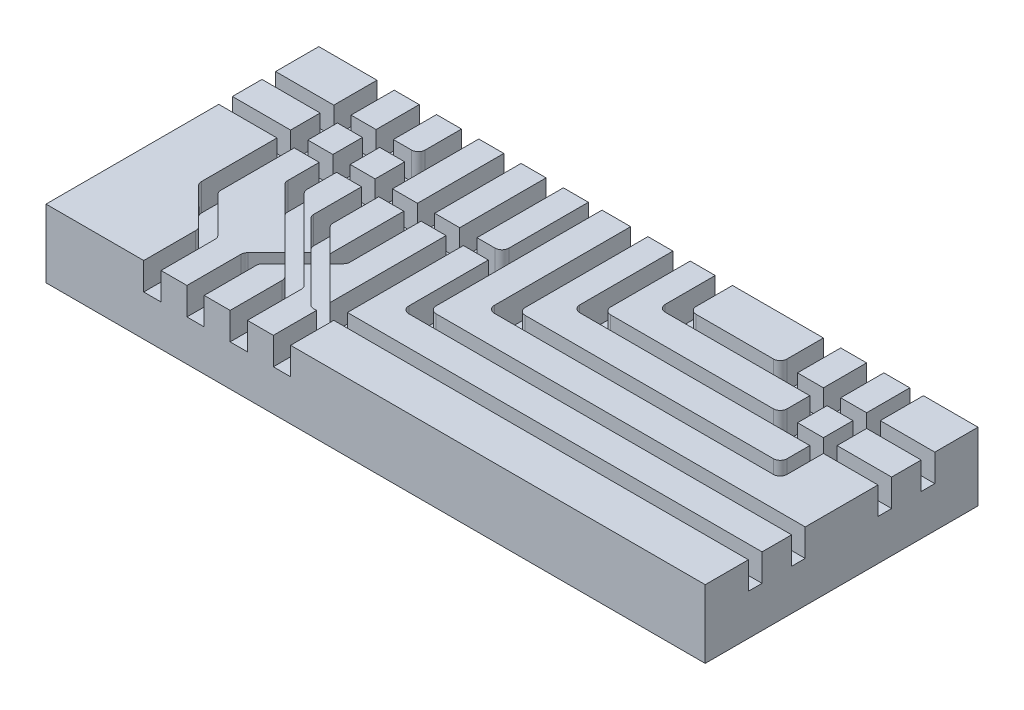
SolidWorks part; units mm, degrees
ref_plane "Front Plane" through (0, 0, 0) normal (0, 0, 1) x (1, 0, 0)
ref_plane "Top Plane" through (0, 0, 0) normal (0, 1, 0) x (1, 0, 0)
ref_plane "Right Plane" through (0, 0, 0) normal (1, 0, 0) x (0, 0, -1)
sketch "Sketch1" plane through (0, 0, 0) normal (0, 1, 0) x (1, 0, 0)
  line L1 (0, 0) -> (145, 0)
  line L2 (0, 0) -> (0, 60)
  line L3 (0, 60) -> (145, 60)
  line L4 (145, 0) -> (145, 60)
  dimension "D1" = 60
  dimension "D2" = 145
extrude "ProfileBoss-Extrude1" add sketch "Sketch1" along normal blind 15
sketch "Sketch2" plane through (0, 15, 0) normal (0, 1, 0) x (1, 0, 0)
  line L0 (25.9, 60) -> (22.1, 60)
  line L1 (53.8, 60) -> (53.8, 41)
  line L7 (53.8, 0) -> (50, 0)
  line L9 (16.6, 60) -> (12.8, 60)
  line L14 (72.4, 60) -> (72.4, 31.5)
  line L15 (72.4, 31.5) -> (130, 31.5)
  line L16 (130, 31.5) -> (130, 38)
  line L17 (130, 60) -> (133, 60)
  line L18 (133, 60) -> (133, 50.5)
  line L19 (133, 28.5) -> (68.6, 28.5)
  line L20 (68.6, 28.5) -> (68.6, 60)
  line L21 (68.6, 60) -> (72.4, 60)
  line L22 (77.9, 60) -> (77.9, 38)
  line L24 (124.3, 41) -> (124.3, 47.5)
  line L25 (124.3, 60) -> (120.5, 60)
  line L26 (120.5, 60) -> (120.5, 50.5)
  line L28 (81.7, 41) -> (81.7, 60)
  line L29 (81.7, 60) -> (77.9, 60)
  line L30 (87.2, 60) -> (87.2, 47.5)
  line L32 (114.8, 50.5) -> (114.8, 60)
  line L33 (114.8, 60) -> (111, 60)
  line L34 (111, 60) -> (111, 50.5)
  line L36 (91, 50.5) -> (91, 60)
  line L37 (91, 60) -> (87.2, 60)
  line L39 (50, 60) -> (53.8, 60)
  line L41 (21.5, 0) -> (25.3, 0)
  line L46 (145, 0) -> (145, 60) construction
  line L51 (44.5, 60) -> (40.7, 60)
  line L52 (145, 60) -> (0, 60) construction
  line L53 (34.8, 0) -> (31, 0)
  line L54 (40.5, 0) -> (44.3, 0)
  line L58 (50, 0) -> (50, 9.5)
  line L63 (0, 0) -> (145, 0) construction
  line L66 (91, 50.5) -> (111, 50.5)
  line L67 (87.2, 47.5) -> (120.5, 47.5)
  line L68 (145, 50.5) -> (145, 47.5)
  line L69 (114.8, 50.5) -> (120.5, 50.5)
  line L70 (120.5, 47.5) -> (120.5, 41)
  line L71 (124.3, 50.5) -> (124.3, 60)
  line L72 (124.3, 47.5) -> (130, 47.5)
  line L73 (124.3, 50.5) -> (130, 50.5)
  line L74 (133, 50.5) -> (145, 50.5)
  line L75 (130, 50.5) -> (130, 60)
  line L76 (133, 47.5) -> (145, 47.5)
  line L77 (133, 47.5) -> (133, 41)
  line L78 (81.7, 41) -> (120.5, 41)
  line L79 (145, 41) -> (145, 38)
  line L80 (145, 38) -> (133, 38)
  line L81 (124.3, 41) -> (130, 41)
  line L82 (130, 41) -> (130, 47.5)
  line L83 (133, 41) -> (145, 41)
  line L84 (130, 38) -> (77.9, 38)
  line L85 (133, 38) -> (133, 28.5)
  line L86 (59.3, 60) -> (62.3, 60)
  line L87 (62.3, 60) -> (62.3, 22)
  line L88 (62.3, 22) -> (145, 22)
  line L89 (145, 22) -> (145, 19)
  line L90 (145, 19) -> (59.3, 19)
  line L91 (59.3, 19) -> (59.3, 38)
  line L93 (145, 12.5) -> (145, 9.5)
  line L94 (145, 9.5) -> (53.8, 9.5)
  line L95 (16.6, 60) -> (16.6, 50.5)
  line L97 (25.3, 12.5) -> (25.3, 0)
  line L98 (21.5, 0) -> (21.5, 12.0574)
  line L100 (12.8, 20.7574) -> (12.8, 38)
  line L101 (22.1, 60) -> (22.1, 50.5)
  line L104 (25.9, 60) -> (25.9, 50.5)
  line L109 (40.7, 60) -> (40.7, 41)
  line L110 (44.5, 60) -> (44.5, 41)
  line L113 (40.5, 12.0574) -> (40.5, 0)
  line L117 (50, 12.5) -> (50, 38)
  line L118 (53.8, 12.5) -> (145, 12.5)
  line L120 (53.8, 9.5) -> (53.8, 0)
  line L121 (31.4, 26.8574) -> (31.4, 38)
  line L122 (31.4, 60) -> (35.2, 60)
  line L123 (35.2, 60) -> (35.2, 41)
  line L134 (50, 12.5) -> (42.6213, 19.8787)
  line L135 (44.3, 12.5) -> (39.7713, 17.0287)
  line L140 (22.1, 30.4574) -> (35.5287, 17.0287)
  line L141 (50, 9.5) -> (48.7574, 9.5)
  line L143 (31.4, 26.8574) -> (38.3787, 19.8787)
  line L144 (31, 0) -> (31, 12.5)
  line L145 (34.8, 0) -> (34.8, 12.0574)
  line L146 (44.3, 0) -> (44.3, 12.5)
  line L147 (31, 12.5) -> (35.5287, 17.0287)
  line L148 (44.5, 21.7574) -> (42.6213, 19.8787)
  line L149 (25.3, 12.5) -> (16.6, 21.2)
  line L150 (21.5, 12.0574) -> (12.8, 20.7574)
  line L151 (37.65, 19.15) -> (38.3787, 19.8787)
  line L152 (37.65, 14.9074) -> (40.5, 12.0574)
  line L153 (37.65, 19.15) -> (25.9, 30.9)
  line L154 (40.7, 21.8) -> (35.2, 27.3)
  line L155 (40.5, 17.7574) -> (39.7713, 17.0287)
  line L156 (40.5, 17.7574) -> (48.7574, 9.5)
  line L157 (37.65, 14.9074) -> (34.8, 12.0574)
  line L158 (31.4, 50.5) -> (25.9, 50.5)
  line L159 (0, 60) -> (0, 0) construction
  line L160 (0, 50.5) -> (0, 47.5)
  line L161 (0, 47.5) -> (12.8, 47.5)
  line L162 (59.3, 41) -> (53.8, 41)
  line L163 (0, 41) -> (0, 38)
  line L164 (0, 38) -> (12.8, 38)
  line L165 (12.8, 50.5) -> (12.8, 60)
  line L166 (16.6, 47.5) -> (22.1, 47.5)
  line L167 (16.6, 47.5) -> (16.6, 41)
  line L168 (12.8, 50.5) -> (0, 50.5)
  line L169 (22.1, 50.5) -> (16.6, 50.5)
  line L170 (25.9, 47.5) -> (31.4, 47.5)
  line L171 (22.1, 47.5) -> (22.1, 41)
  line L172 (25.9, 47.5) -> (25.9, 41)
  line L173 (31.4, 50.5) -> (31.4, 60)
  line L174 (12.8, 41) -> (0, 41)
  line L175 (16.6, 38) -> (22.1, 38)
  line L176 (12.8, 41) -> (12.8, 47.5)
  line L177 (16.6, 38) -> (16.6, 21.2)
  line L178 (22.1, 38) -> (22.1, 30.4574)
  line L179 (25.9, 38) -> (25.9, 30.9)
  line L180 (22.1, 41) -> (16.6, 41)
  line L181 (25.9, 38) -> (31.4, 38)
  line L182 (31.4, 41) -> (31.4, 47.5)
  line L183 (31.4, 41) -> (25.9, 41)
  line L184 (35.2, 38) -> (35.2, 27.3)
  line L185 (35.2, 38) -> (40.7, 38)
  line L186 (40.7, 38) -> (40.7, 21.8)
  line L187 (44.5, 38) -> (44.5, 21.7574)
  line L188 (40.7, 41) -> (35.2, 41)
  line L189 (44.5, 38) -> (50, 38)
  line L190 (53.8, 38) -> (59.3, 38)
  line L191 (50, 41) -> (50, 60)
  line L192 (53.8, 38) -> (53.8, 12.5)
  line L193 (59.3, 41) -> (59.3, 60)
  line L194 (50, 41) -> (44.5, 41)
  point P104 (-44.2777, 79.5421)
  dimension "D2" = 9.3
  dimension "D4" = 9.5
  dimension "D5" = 9.3
  dimension "D3" = 9.5
  dimension "D1" = 3
  dimension "D9" = 12
  dimension "D10" = 20
  dimension "D8" = 9.3
  dimension "D13" = 3
  dimension "D19" = 12.8
  dimension "D14" = 9.5
  dimension "D15" = 9.5
  dimension "D16" = 9.5
  dimension "D18" = 9.5
  dimension "D7" = 9.3
  dimension "D12" = 9.3
  dimension "D21" = 3
  dimension "D22" = 9.5
  dimension "D17" = 9.3
  dimension "D20" = 3
  dimension "D23" = 135
  dimension "D24" = 3
  dimension "D25" = 135
  dimension "D26" = 3
  dimension "D27" = 9.5
  dimension "D28" = 9.5
  dimension "D29" = 9.5
  dimension "D30" = 95
  dimension "D31" = 9.5
  dimension "D11" = 9.3
  dimension "D32" = 9.3
extrude "LeedCut-Extrude1" cut sketch "Sketch2" against normal blind 6
sketch "MountHoleSketch3" plane through (0, 0, 0) normal (0, 1, 0) x (1, 0, 0)
  line L0 (0, 60) -> (0, 50.5) construction
  line L2 (12.8, 60) -> (0, 60) construction
  line L3 (145, 0) -> (145, 9.5) construction
  circle A0 centre (6, 30) radius 2.05
  circle A1 centre (139, 30) radius 2.05
  dimension "D4" = 4.1
  dimension "D3" = 30
  dimension "D2" = 133
  dimension "D5" = 6
fillet "Fillet1" radius 1.5 8 edges at (87.2, 12, -47.5) (59.3, 12, -19) (68.6, 12, -28.5) (77.9, 12, -38) (62.3, 12, -22) (72.4, 12, -31.5) (81.7, 12, -41) (91, 12, -50.5)
fillet "Fillet2" radius 1.5 6 edges at (130, 12, -31.5) (120.5, 12, -41) (111, 12, -50.5) (133, 12, -28.5) (59.3, 12, -41) (31.4, 12, -50.5)
fillet "Fillet3" radius 1.5 14 edges at (25.3, 12, -12.5) (34.8, 12, -12.0574) (31.4, 12, -26.8574) (12.8, 12, -20.7574) (21.5, 12, -12.0574) (31, 12, -12.5) (44.3, 12, -12.5) (40.5, 12, -12.0574) (48.7574, 12, -9.5) (16.6, 12, -21.2) (35.2, 12, -27.3) (25.9, 12, -30.9) (22.1, 12, -30.4574) (44.5, 12, -21.7574)
extrude "MountHoleCut-Extrude2" cut sketch "MountHoleSketch3" against normal blind 0.1 and the other way blind 3.1
equation "\"D2@Sketch1\" = \"PowerCableGuideWidth\""
equation "\"PowerCableGuideWidth\"= IIF ( \"DistanceBetween24vPowerSupplyLeads\" * \"NumberOfPowerLeadSpaces\" + \"PowerCableDiameter\" * 2 + \"DistanceFromCaseToFirstPowerTerminal\" + \"PowerCableGuideMountSupportWidth\" * 2 , 145mm , 145mm )'Keep the width 145mm based on the original Distanceetween24vPowerSupplyLeads being 9.5mm"
equation "\"PowerCableGuideLength\"= 60mm"
equation "\"PowerCableDiameter\"= 3mm"
equation "\"NumberOfPowerLeadSpaces\"= 10"
equation "\"M3HeatInsertHoleDiameter\"= 4mm + .1mm'Add .1mm for printing"
equation "\"DistanceBetween24vPowerSupplyLeads\"= 9.3mm'Spec"
equation "\"PowerCableGuideDepth\"= 15mm"
equation "\"DistanceFromCaseToFirstPowerTerminal\"= 13mm + \"PowreCableGuideAdditionalPowerWidth\""
equation "\"PowerCableGuideMountSupportWidth\"= 12mm"
equation "\"D1@Sketch1\"=\"PowerCableGuideLength\""
equation "\"D1@ProfileBoss-Extrude1\" = \"PowerCableGuideDepth\""
equation "\"D1@LeedCut-Extrude1\" = \"PowerCableDiameter\" * 2"
equation "\"D2@Sketch2\"=\"DistanceBetween24vPowerSupplyLeads\""
equation "\"D4@Sketch2\"=\"DistanceBetweenOutgoingPowerSupplyLeeds\""
equation "\"D5@Sketch2\"=\"DistanceBetween24vPowerSupplyLeads\""
equation "\"D3@Sketch2\"=\"DistanceBetweenOutgoingPowerSupplyLeeds\""
equation "\"D1@Sketch2\"=\"PowerCableDiameter\""
equation "\"D8@Sketch2\"=\"DistanceBetween24vPowerSupplyLeads\""
equation "\"D9@Sketch2\"=\"PowerCableGuideMountSupportWidth\""
equation "\"D13@Sketch2\"=\"PowerCableDiameter\""
equation "\"D10@Sketch2\"=\"DistanceFromCaseToFirstPowerTerminal\""
equation "\"PowreCableGuideAdditionalPowerWidth\"= 7mm"
equation "\"D3@MountHoleSketch3\" = \"PowerCableGuideLength\" / 2"
equation "\"D4@MountHoleSketch3\" = \"M3HeatInsertHoleDiameter\""
equation "\"PowerCableGuideMountHoleDistanceBetween\"= \"PowerCableGuideWidth\" - \"PowerCableGuideMountSupportWidth\""
equation "\"D2@MountHoleSketch3\" = \"PowerCableGuideMountHoleDistanceBetween\""
equation "\"D1@MountHoleSketch3\" = \"PowerCableGuideMountSupportWidth\" / 2"
equation "\"D14@Sketch2\"=\"DistanceBetweenOutgoingPowerSupplyLeeds\""
equation "\"D15@Sketch2\"=\"DistanceBetweenOutgoingPowerSupplyLeeds\""
equation "\"D16@Sketch2\"=\"DistanceBetweenOutgoingPowerSupplyLeeds\""
equation "\"D18@Sketch2\"=\"DistanceBetweenOutgoingPowerSupplyLeeds\""
equation "\"D7@Sketch2\"=\"DistanceBetween24vPowerSupplyLeads\""
equation "\"D22@Sketch2\"=\"DistanceBetweenOutgoingPowerSupplyLeeds\""
equation "\"D17@Sketch2\"=\"DistanceBetween24vPowerSupplyLeads\""
equation "\"M3HeatInsertHoleDepth\"= 4mm"
equation "\"DistanceBetweenOctopusPowerSupplyLeeds\"= 9.5mm"
equation "\"D29@Sketch2\"=\"DistanceBetweenOctopusPowerSupplyLeeds\""
equation "\"DistanceToFirstOctopusPowerSupplyLeed\"= 95mm"
equation "\"D30@Sketch2\"=\"DistanceToFirstOctopusPowerSupplyLeed\""
equation "\"D28@Sketch2\"=\"DistanceBetweenOctopusPowerSupplyLeeds\""
equation "\"D31@Sketch2\"=\"DistanceBetweenOctopusPowerSupplyLeeds\""
equation "\"DistanceBetweenOutgoingPowerSupplyLeeds\"= 9.5mm"
equation "\"D12@Sketch2\"=\"DistanceBetween24vPowerSupplyLeads\""
equation "\"D11@Sketch2\"=\"DistanceBetween24vPowerSupplyLeads\""
equation "\"D32@Sketch2\"=\"DistanceBetween24vPowerSupplyLeads\""
